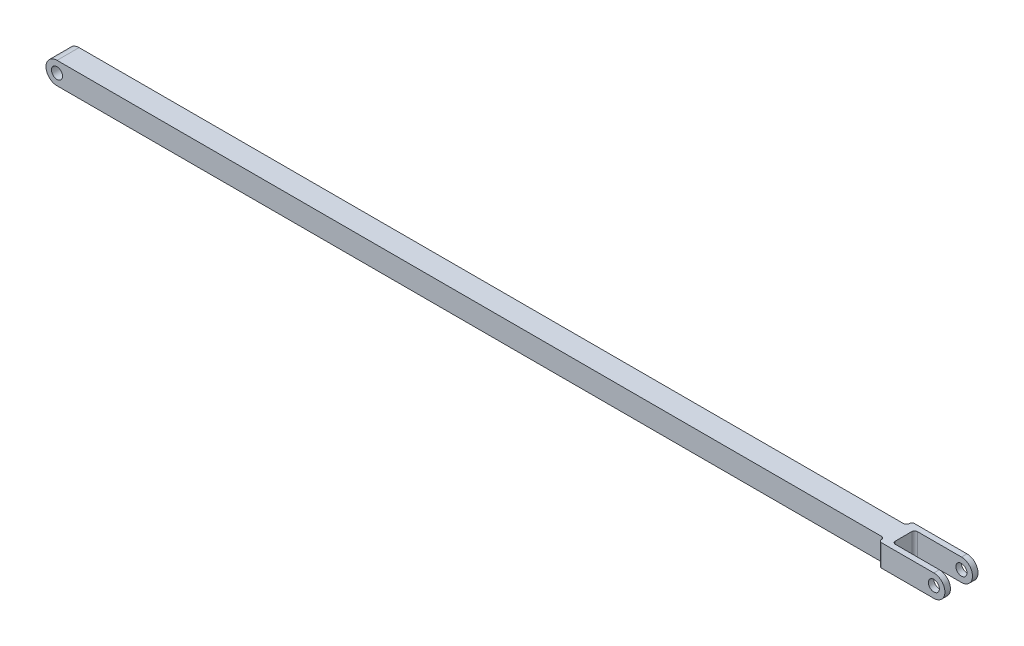
SolidWorks part; units mm, degrees
ref_plane "Front Plane" through (0, 0, 0) normal (0, 0, 1) x (1, 0, 0)
ref_plane "Top Plane" through (0, 0, 0) normal (0, 1, 0) x (1, 0, 0)
ref_plane "Right Plane" through (0, 0, 0) normal (1, 0, 0) x (0, 0, -1)
sketch "Sketch1" plane through (0, 0, 0) normal (0, 0, 1) x (1, 0, 0)
  line L0 (-508, 0) -> (508, 0) construction
  line L1 (-508, 12.7) -> (508, 12.7)
  line L2 (-508, -12.7) -> (508, -12.7)
  arc A0 (-508, 12.7) -> (-508, -12.7) centre (-508, 0) ccw
  arc A1 (508, -12.7) -> (508, 12.7) centre (508, 0) ccw
  point P3 (0, 0)
  dimension "D2" = 1016
  dimension "D1" = 25.4
extrude "Boss-Extrude1" add sketch "Sketch1" along normal mid plane 25.4
sketch "Sketch2" plane through (0, 0, 12.7) normal (0, 0, 1) x (1, 0, 0)
  line L2 (-508, -12.7) -> (508, -12.7)
  line L3 (508, 12.7) -> (-508, 12.7)
  line L4 (-508, -12.7) -> (508, -12.7)
  line L5 (508, 12.7) -> (-508, 12.7)
  circle A0 centre (-508, 0) radius 6.35
  circle A1 centre (508, 0) radius 6.35
  arc A2 (-508, 12.7) -> (-508, -12.7) centre (-508, 0) ccw
  arc A3 (508, -12.7) -> (508, 12.7) centre (508, 0) ccw
  arc A4 (-508, 12.7) -> (-508, -12.7) centre (-508, 0) ccw
  arc A5 (508, -12.7) -> (508, 12.7) centre (508, 0) ccw
  dimension "D2" = 12.7
  dimension "D3" = 12.7
  dimension "D1" = 0
extrude "Cut-Extrude1" cut sketch "Sketch2" against normal through all contours A0 | A1 region at (-508, 0, 12.7) region at (508, 0, 12.7)
sketch "Sketch3" plane through (0, 12.7, 0) normal (0, 1, 0) x (1, 0, 0)
  line L0 (501.65, -12.7) -> (514.35, -12.7) construction
  line L1 (501.65, -12.7) -> (514.35, -12.7)
  line L2 (0, 0) -> (508, 0)
  line L4 (508, 12.7) -> (-508, 12.7)
  line L5 (-508, 12.7) -> (-508, -12.7)
  line L6 (-508, -12.7) -> (508, -12.7)
  line L7 (508, -12.7) -> (508, 12.7)
  line L8 (508, 12.7) -> (-508, 12.7)
  line L9 (-508, 12.7) -> (-508, -12.7)
  line L10 (-508, -12.7) -> (508, -12.7)
  line L11 (508, -12.7) -> (508, 12.7)
  line L12 (520.7, 19.05) -> (444.5, 19.05)
  line L13 (520.7, 19.05) -> (520.7, -19.05)
  line L14 (520.7, -19.05) -> (444.5, -19.05)
  line L15 (444.5, 19.05) -> (444.5, -19.05)
  line L16 (520.7, 19.05) -> (444.5, -19.05) construction
  line L17 (520.7, -19.05) -> (444.5, 19.05) construction
  point P8 (482.6, 0)
  dimension "D2" = 38.1
  dimension "D3" = 76.2
  dimension "D1" = 0
extrude "Boss-Extrude4" add sketch "Sketch3" against normal through all contours L12 L15 L14 L13
sketch "Sketch6" plane through (0, 12.7, 0) normal (0, 1, 0) x (1, 0, 0)
  line L0 (520.7, 19.05) -> (520.7, -19.05) construction
  line L1 (454.025, 12.7) -> (520.7, 12.7)
  line L2 (454.025, 12.7) -> (454.025, -12.7)
  line L3 (454.025, -12.7) -> (520.7, -12.7)
  line L4 (520.7, 12.7) -> (520.7, -12.7)
  line L6 (444.5, 19.05) -> (444.5, 12.7) construction
  line L7 (520.7, -19.05) -> (444.5, -19.05) construction
  line L8 (520.7, 19.05) -> (444.5, 19.05) construction
  dimension "D1" = 9.525
  dimension "D2" = 6.35
  dimension "D3" = 6.35
extrude "Cut-Extrude3" cut sketch "Sketch6" against normal through all contours L3 L4 L1 L2
sketch "Sketch4" plane through (0, 0, 19.05) normal (0, 0, 1) x (1, 0, 0)
  line L4 (520.7, 12.7) -> (444.5, 12.7)
  line L5 (520.7, 12.7) -> (444.5, 12.7)
  line L6 (444.5, -12.7) -> (520.7, -12.7)
  line L7 (520.7, -12.7) -> (520.7, 12.7)
  line L8 (444.5, 12.7) -> (444.5, -12.7)
  line L9 (444.5, 12.7) -> (444.5, -12.7)
  line L10 (444.5, -12.7) -> (520.7, -12.7)
  line L11 (520.7, -12.7) -> (520.7, 12.7)
  circle A0 centre (-508, 0) radius 6.35 construction
  circle A1 centre (-508, 0) radius 6.35
  circle A2 centre (508, 0) radius 6.35
  circle A3 centre (508, 0) radius 12.7
  line M1 (520.7, 12.7) -> (444.5, 12.7)
  line M4 (520.7, -12.7) -> (520.7, 12.7)
  dimension "D1" = 12.7
  dimension "D2" = 1016
  dimension "D3" = 0
extrude "Cut-Extrude2" cut sketch "Sketch4" against normal through all contours A3 L11 M1 | A3 L10 M4 | A2 region at (517.8632, 9.8632, 19.05) region at (517.8632, -9.8632, 19.05)
fillet "Fillet3" radius 3.175 6 edges at (454.025, 0, 12.7) (444.5, 0, -19.05) (444.5, 0, -12.7) (444.5, 0, 12.7) (454.025, 0, -12.7) (444.5, 0, 19.05)
equation "\"D2@Sketch4\"=\"D2@Sketch1\""
